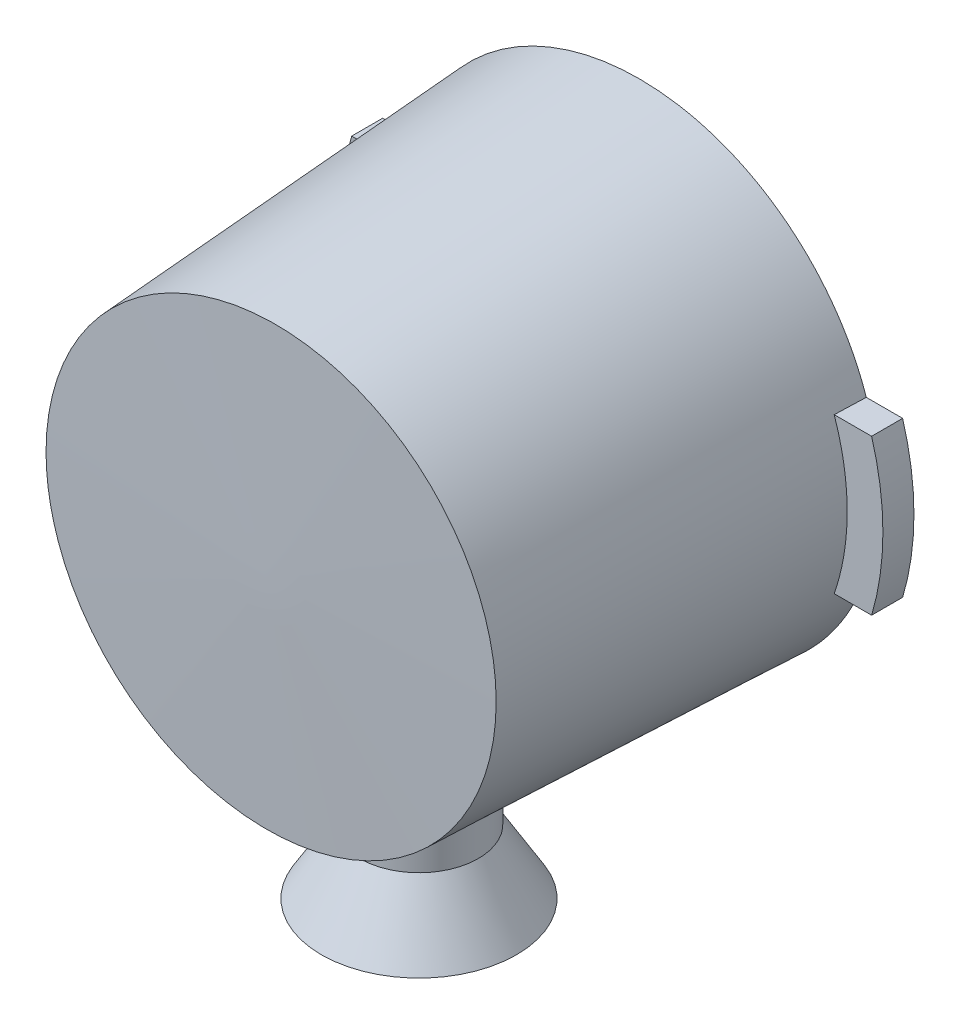
SolidWorks part; units mm, degrees
ref_plane "Front Plane" through (0, 0, 0) normal (0, 0, 1) x (1, 0, 0)
ref_plane "Top Plane" through (0, 0, 0) normal (0, 1, 0) x (1, 0, 0)
ref_plane "Right Plane" through (0, 0, 0) normal (1, 0, 0) x (0, 0, -1)
sketch "Sketch1" plane through (0, 0, 0) normal (0, 0, 1) x (1, 0, 0)
  line L0 (-50.9943, 48.8899) -> (-50.9943, -61.1101)
  line L1 (-50.9943, -61.1101) -> (-36.9943, -61.1101)
  line L2 (-50.9943, 48.8899) -> (-37.9943, 48.8899)
  line L3 (-37.9943, 48.8899) -> (-36.9943, -61.1101)
  dimension "D1" = 110
  dimension "D2" = 14
  dimension "D3" = 13
ref_plane "Plane2" through (0, 48.4713, 0) normal (0, 1, 0) x (1, 0, 0)
sketch "Sketch2" plane through (0, 48.4713, 0) normal (0, 1, 0) x (1, 0, 0)
  line L0 (-37.9036, -0.7321) -> (-37.6929, -6.4334) construction
  line L1 (-23.3018, -0.1923) -> (-23.091, -5.8936)
  line L2 (-52.5055, -1.2719) -> (-52.2947, -6.9731)
  arc A0 (-23.3018, -0.1923) -> (-52.5055, -1.2719) centre (-37.9036, -0.7321) ccw
  arc A1 (-52.2947, -6.9731) -> (-23.091, -5.8936) centre (-37.6929, -6.4334) ccw
  point P2 (-37.7982, -3.5827)
  point P3 (-51.1046, 4.5825)
sketch "Sketch3" plane through (0, 0, 0) normal (0, 0, 1) x (1, 0, 0)
  line L1 (-23.081, 51.4713) -> (-52.2947, 51.4713) construction
  line L4 (-45.3454, 59.7527) -> (-50.2855, 51.4713)
  line L5 (-50.2855, 51.4713) -> (-37.6879, 51.4713)
  line L6 (-37.6879, 51.4713) -> (-37.6879, 71.3127)
  line L7 (-45.3454, 59.7527) -> (-45.3454, 71.3127)
  line L8 (-45.3454, 71.3127) -> (-37.6879, 71.3127)
revolve "Revolve4" add sketch "Sketch3" angle 360 about L6
ref_plane "Plane4" through (0, 97.3127, 0) normal (0, 1, 0) x (1, 0, 0)
sketch "Sketch5" plane through (0, 97.3127, 0) normal (0, 1, 0) x (1, 0, 0)
  line L0 (-37.6879, 0) -> (-37.303, -20)
  line L1 (-37.6879, 0) -> (-38.2653, 30)
  line L2 (-38.2653, 30) -> (-69.2653, 29.4034)
  line L3 (-37.303, -20) -> (-65.803, -20)
  line L4 (-69.2653, 29.4034) -> (-65.803, -20)
  dimension "D1" = 20
  dimension "D2" = 30
  dimension "D3" = 28.5
  dimension "D4" = 31
revolve "Revolve5" add sketch "Sketch5" angle 360 about L1
sketch "Sketch6" plane through (0, 97.3127, 0) normal (0, 1, 0) x (1, 0, 0)
  line L0 (-37.3703, -16.5006) -> (-62.5088, -16.9409)
  line L1 (-37.6879, 0) -> (-37.303, -20) construction
  line L2 (-69.2653, 29.4034) -> (-65.803, -20) construction
  line L3 (-62.5088, -16.9409) -> (-65.7653, 30.5314)
  line L4 (-65.7653, 30.5314) -> (-38.2857, 31.0603)
  line L5 (-38.2857, 31.0603) -> (-37.3703, -16.5006)
  dimension "D1" = 3.5
  dimension "D2" = 3.5
  dimension "D3" = 3.5
ref_plane "Plane6" through (0, 0, -25) normal (0, 0, 1) x (1, 0, 0)
sketch "Sketch9" plane through (0, 0, -25) normal (0, 0, 1) x (1, 0, 0)
  line L0 (-38.2857, 97.3127) -> (-37.3703, 97.3127) construction
  line L1 (-8.9475, 107.3127) -> (-9.7611, 107.3127)
  line L2 (-9.7611, 107.3127) -> (-9.7611, 87.3127)
  line L3 (-66.7084, 107.3127) -> (-71.369, 107.3127)
  line L4 (-66.7084, 87.3127) -> (-71.369, 87.3127)
  line L5 (-8.9475, 107.3127) -> (-4.287, 107.3127)
  line L6 (-8.9475, 87.3127) -> (-4.287, 87.3127)
  line L7 (-9.7611, 87.3127) -> (-8.9475, 87.3127)
  circle A1 centre (-37.828, 97.3127) radius 30.5627
  arc A2 (-71.369, 107.3127) -> (-71.369, 87.3127) centre (-37.828, 97.3127) ccw
  arc A3 (-4.287, 87.3127) -> (-4.287, 107.3127) centre (-37.828, 97.3127) ccw
ref_plane "Plane7" through (0, 0, -29.0038) normal (0, 0, 1) x (1, 0, 0)
sketch "Sketch10" plane through (0, 0, -29.0038) normal (0, 0, 1) x (1, 0, 0)
  line L1 (-85.8916, 143.5647) -> (14.126, 143.5647)
  line L2 (-85.8916, 143.5647) -> (-85.8916, 61.3072)
  line L3 (-85.8916, 61.3072) -> (14.126, 61.3072)
  line L4 (14.126, 143.5647) -> (14.126, 61.3072)
extrude "Boss-Extrude9" add sketch "Sketch9" against normal blind 5 contours L7 A1 L1 L2 | L6 A3 L5 A1 | L3 A2 L4 A1 region at (-8.7261, 97.3127, -25) region at (-5.5717, 97.3127, -25) region at (-70.0842, 97.3127, -25)
extrude "Cut-Extrude5" cut sketch "Sketch10" against normal blind 5
revolve "Cut-Revolve4" cut sketch "Sketch6" angle 360 about L5
ref_plane "Plane8" through (0, 0, -29.0038) normal (0, 0, -1) x (-1, 0, 0)
